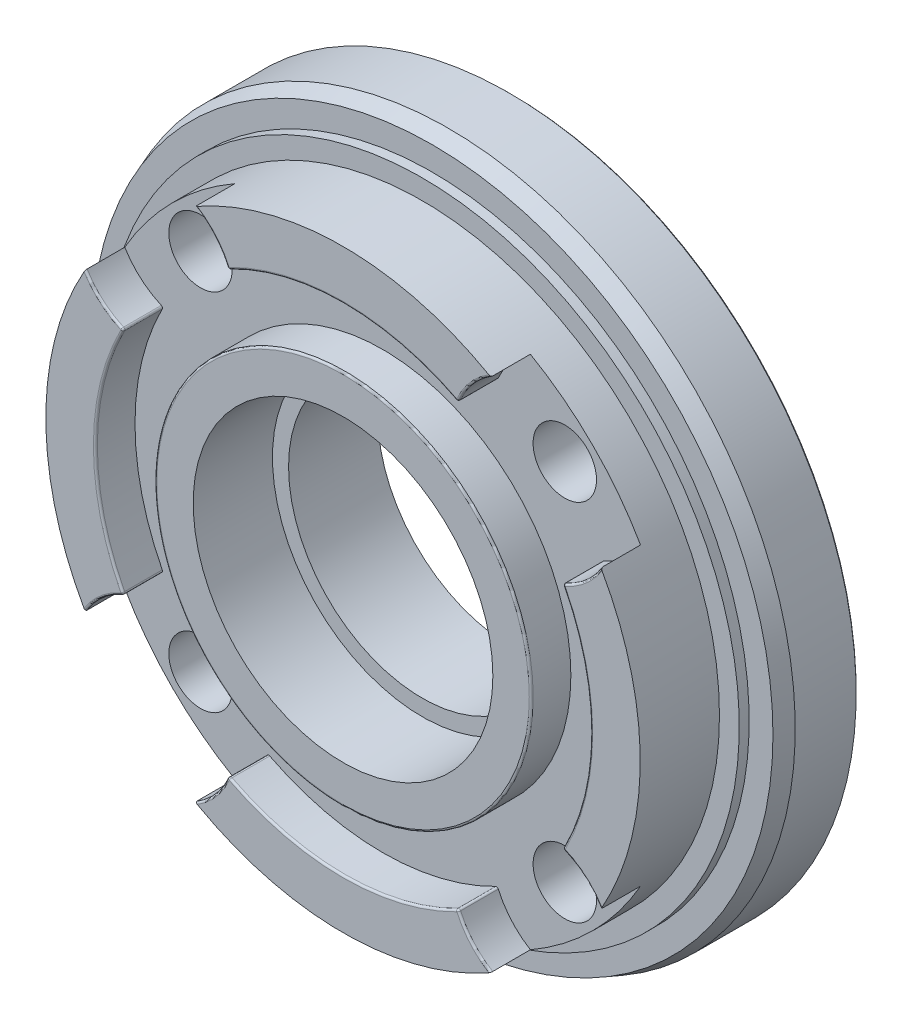
SolidWorks part; units mm, degrees
material "ABS"
ref_plane "Front Plane" through (0, 0, 0) normal (0, 0, 1) x (1, 0, 0)
ref_plane "Top Plane" through (0, 0, 0) normal (0, 1, 0) x (1, 0, 0)
ref_plane "Right Plane" through (0, 0, 0) normal (1, 0, 0) x (0, 0, -1)
sketch "Sketch1" plane through (0, 0, 0) normal (0, 0, 1) x (1, 0, 0)
  line L0 (0, 0) -> (13.5, 0) construction
  line L1 (0, 0) -> (9.5459, 9.5459) construction
  circle A0 centre (0, 0) radius 9.5
  circle A1 centre (0, 0) radius 15
  arc A2 (-6.285, 11.9478) -> (-11.9478, 6.285) centre (0, 0) ccw construction
  arc A3 (7.4565, 13.0154) -> (5.7957, 11.0752) centre (9.5459, 9.5459) ccw
  arc A4 (13.0154, -7.4565) -> (11.0752, -5.7957) centre (9.5459, -9.5459) ccw
  arc A5 (-7.4565, -13.0154) -> (-5.7957, -11.0752) centre (-9.5459, -9.5459) ccw
  arc A6 (-13.0154, 7.4565) -> (-11.0752, 5.7957) centre (-9.5459, 9.5459) ccw
  arc A7 (-11.0752, 5.7957) -> (-11.0752, -5.7957) centre (0, 0) ccw
  arc A8 (11.9478, 6.285) -> (6.285, 11.9478) centre (0, 0) ccw construction
  arc A9 (6.285, -11.9478) -> (11.9478, -6.285) centre (0, 0) ccw construction
  arc A10 (-11.9478, -6.285) -> (-6.285, -11.9478) centre (0, 0) ccw construction
  arc A11 (5.7957, 11.0752) -> (-5.7957, 11.0752) centre (0, 0) ccw
  arc A12 (-5.7957, -11.0752) -> (5.7957, -11.0752) centre (0, 0) ccw
  arc A13 (11.0752, -5.7957) -> (11.0752, 5.7957) centre (0, 0) ccw
  arc A14 (-5.7957, 11.0752) -> (-7.4565, 13.0154) centre (-9.5459, 9.5459) ccw
  arc A15 (11.0752, 5.7957) -> (13.0154, 7.4565) centre (9.5459, 9.5459) ccw
  arc A16 (5.7957, -11.0752) -> (7.4565, -13.0154) centre (9.5459, -9.5459) ccw
  arc A17 (-11.0752, -5.7957) -> (-13.0154, -7.4565) centre (-9.5459, -9.5459) ccw
  circle A18 centre (0, 0) radius 7.5625
  point P17 (0, 0)
  dimension "D1" = 19
  dimension "D2" = 30
  dimension "D3" = 27
  dimension "D4" = 45
  dimension "D5" = 8.1
  dimension "D6" = 4
  dimension "D7" = 25
  dimension "D8" = 15.125
extrude "Boss-Extrude1" add sketch "Sketch1" along normal blind 2 contours A14 A11 A3 A1 | A15 A13 A4 A1 | A16 A12 A5 A1 | A17 A7 A6 A1 | A0 A18 region at (-9.2313, 0, 0) region at (13.2504, 0, 0) region at (0, 13.2504, 0) region at (0, -13.2504, 0) region at (-13.2504, 0, 0)
sketch "Sketch2" plane through (0, 0, 0) normal (0, 0, 1) x (1, 0, 0)
  circle A0 centre (0, 0) radius 15
extrude "Boss-Extrude2" add sketch "Sketch2" against normal blind 2
fillet "Fillet1" radius 0.1 8 edges at (-5.7957, -11.0752, 1) (5.7957, -11.0752, 1) (11.0752, -5.7957, 1) (11.0752, 5.7957, 1) (5.7957, 11.0752, 1) (-5.7957, 11.0752, 1) (-11.0752, 5.7957, 1) (-11.0752, -5.7957, 1)
fillet "Fillet2" radius 0.1 21 edges at (6.5042, 12.2199, 2) (5.7793, 11.1194, 2) (-6.5042, 12.2199, 2) (-5.7793, 11.1194, 2) (12.2199, -6.5042, 2) (11.1194, -5.7793, 2) (12.2199, 6.5042, 2) (11.1194, 5.7793, 2) (-6.5042, -12.2199, 2) (-5.7793, -11.1194, 2) (6.5042, -12.2199, 2) (5.7793, -11.1194, 2) (-12.2199, 6.5042, 2) (-11.1194, 5.7793, 2) (-12.2199, -6.5042, 2) (-11.1194, -5.7793, 2) (0, 12.5, 2) (12.5, 0, 2) (0, -12.5, 2) (9.5, 0, 2) (-12.5, 0, 2)
sketch "Sketch3" plane through (0, 0, -2) normal (0, 0, -1) x (-1, 0, 0)
  line L1 (9.1924, 9.1924) -> (-9.1924, 9.1924) construction
  line L2 (-9.1924, 9.1924) -> (-9.1924, -9.1924) construction
  line L3 (-9.1924, -9.1924) -> (9.1924, -9.1924) construction
  line L4 (9.1924, -9.1924) -> (9.1924, 9.1924) construction
  circle A0 centre (0, 0) radius 13 construction
  circle A1 centre (-9.1924, 9.1924) radius 1.6
  circle A2 centre (9.1924, 9.1924) radius 1.6
  circle A3 centre (9.1924, -9.1924) radius 1.6
  circle A4 centre (-9.1924, -9.1924) radius 1.6
  point P17 (0, 0)
  dimension "D1" = 26
  dimension "D2" = 3.2
  dimension "D3" = 4
sketch "Sketch4" plane through (0, 0, -2) normal (0, 0, -1) x (-1, 0, 0)
  circle A0 centre (0, 0) radius 16
  dimension "D1" = 32
extrude "Boss-Extrude3" add sketch "Sketch4" along normal blind 0.5
sketch "Sketch5" plane through (0, 0, -2.5) normal (0, 0, -1) x (-1, 0, 0)
  circle A0 centre (0, 0) radius 17.5
  dimension "D1" = 35
extrude "Boss-Extrude4" add sketch "Sketch5" along normal blind 4
extrude "Cut-Extrude2" cut sketch "Sketch3" against normal through all and the other way through all
sketch "Sketch6" plane through (0, 0, -6.5) normal (0, 0, -1) x (-1, 0, 0)
  circle A0 centre (-9.1924, 9.1924) radius 2.1
  circle A1 centre (9.1924, 9.1924) radius 2.1
  circle A2 centre (9.1924, -9.1924) radius 2.1
  circle A3 centre (-9.1924, -9.1924) radius 2.1
  point P12 (0, 0)
  dimension "D1" = 4.2
  dimension "D2" = 4
extrude "Cut-Extrude3" cut sketch "Sketch6" against normal blind 4
sketch "Sketch7" plane through (0, 0, -6.5) normal (0, 0, -1) x (-1, 0, 0)
  line L0 (0, 0) -> (0, 13) construction
  line L1 (0, 13) -> (-13, 0) construction
  line L2 (-13, 0) -> (0, -13) construction
  line L3 (0, -13) -> (13, 0) construction
  line L4 (13, 0) -> (0, 13) construction
  circle A0 centre (0, 0) radius 13 construction
  circle A1 centre (0, 13) radius 2.6
  circle A2 centre (13, 0) radius 2.6
  circle A3 centre (0, -13) radius 2.6
  circle A4 centre (-13, 0) radius 2.6
  point P17 (0, 0)
  dimension "D1" = 26
  dimension "D2" = 5.2
  dimension "D3" = 4
extrude "Cut-Extrude4" cut sketch "Sketch7" against normal blind 4
sketch "Sketch8" plane through (0, 0, 0) normal (0, 0, 1) x (1, 0, 0)
  circle A0 centre (0, 0) radius 6.75
  dimension "D1" = 13.5
extrude "Middle Cutout" cut sketch "Sketch8" against normal blind 7
chamfer "Chamfer1" distance 0.1 angle 45 1 edges at (-17.5, 0, -6.5)
sketch "Sketch9" plane through (0, 0, 0) normal (0, 0, 1) x (1, 0, 0)
  circle A0 centre (0, 0) radius 7.5625
  dimension "D1" = 15.125
extrude "Cut-Extrude6" cut sketch "Sketch9" against normal blind 2
chamfer "Chamfer2" distance 0.3 angle 70 1 edges at (-17.5, 0, -2.5) first distance on face at (-16, 0, -2.5)
equation "\"RingPinShaft\"= 5.05"
equation "\"CenterBearingOut\"=32.00"
equation "\"OutputBearingOut\"=37.00"
equation "\"RingPostIn\"=5.15"
equation "\"CamBearingOut\"=15.1"
equation "\"DiskOutputShaft\"=10.1"
equation "\"CenterShaft\"=25.2"
equation "\"Eccentricity\"=2"
equation "\"CycCamShaft\"=10.05"
equation "\"m3Thru\"=3.15"
equation "\"m3Insert\"=4.2"
equation "\"D1@Sketch6\"=\"m3Insert\""
